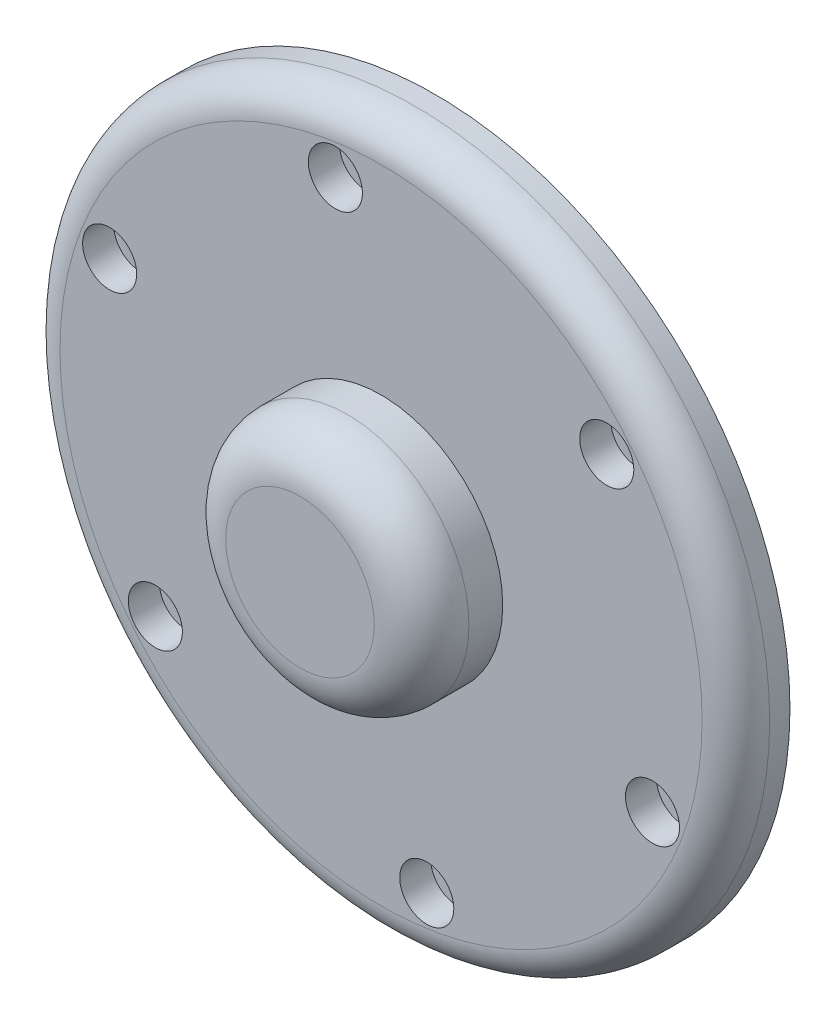
SolidWorks part; units mm, degrees
ref_plane "前视基准面" through (0, 0, 0) normal (0, 0, 1) x (1, 0, 0)
ref_plane "上视基准面" through (0, 0, 0) normal (0, 1, 0) x (1, 0, 0)
ref_plane "右视基准面" through (0, 0, 0) normal (1, 0, 0) x (0, 0, -1)
other "Configuration Table"
sketch "草图1" plane through (0, 0, 0) normal (0, 0, 1) x (1, 0, 0)
  circle A0 centre (0, 0) radius 52.5
  dimension "D1" = 105
extrude "凸台-拉伸1" add sketch "草图1" along normal blind 20
sketch "草图3" plane through (0, 0, 20) normal (0, 0, 1) x (1, 0, 0)
  circle A0 centre (0, 0) radius 52.5
  circle A2 centre (0, 0) radius 18
  dimension "D1" = 105
  dimension "D3" = 36
extrude "切除-拉伸1" cut sketch "草图3" against normal blind 12
sketch "草图5" plane through (0, 0, 0) normal (0, 0, -1) x (-1, 0, 0)
  line L0 (0, 11) -> (0, -11) construction
  circle A0 centre (0, 0.6473) radius 15.25
  dimension "D1" = 30.5
extrude "切除-拉伸3" cut sketch "草图5" against normal blind 17.5
hole_wizard "M4 六角圆柱头螺钉的柱形沉头孔1" positions "草图12" profile "草图13" counterbore size "M4" standard "GB" end condition through all
sketch "草图12" plane through (0, 0, 8) normal (0, 0, 1) x (1, 0, 0)
  point P0 (33.3945, 27.0889)
sketch "草图13" plane through (33.3945, 27.0889, 8) normal (1, 0, 0) x (0, -1, 0)
  line L0 (0, 0) -> (0, 8)
  line L1 (0, 8) -> (2.25, 8)
  line L3 (2.25, 8) -> (2.25, 4.6)
  line L4 (2.25, 4.6) -> (4, 4.6)
  line L5 (4, 4.6) -> (4, 0)
  line L7 (4, 0) -> (0, 0)
  line L11 (0, -6.35) -> (0, 107.95) construction
  dimension "通孔孔直径" = 4.5
  dimension "通孔孔深度" = 8
  dimension "柱形沉头孔直径" = 8
  dimension "柱形沉头孔深度" = 4.6
pattern_circular "阵列(圆周)1" count 6 over 360 about axis through (0, 0, 20) along (0, 0, -1) of "M4 六角圆柱头螺钉的柱形沉头孔1"
fillet "圆角2" radius 7 1 edges at (18, 0, 20)
fillet "圆角3" radius 5 1 edges at (52.5, 0, 8)
